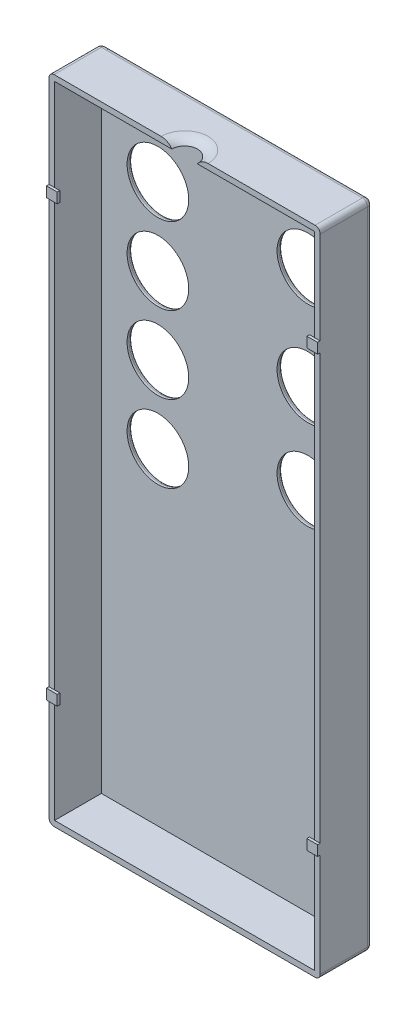
SolidWorks part; units mm, degrees
ref_plane "Plan de face" through (0, 0, 0) normal (0, 0, 1) x (1, 0, 0)
ref_plane "Plan de dessus" through (0, 0, 0) normal (0, 1, 0) x (1, 0, 0)
ref_plane "Plan de droite" through (0, 0, 0) normal (1, 0, 0) x (0, 0, -1)
sketch "Esquisse1" plane through (0, 0, 0) normal (0, 0, 1) x (1, 0, 0)
  line L1 (-28.2911, -78.7359) -> (22.3089, -78.7359)
  line L2 (-28.2911, -78.7359) -> (-28.2911, 45.8641)
  line L3 (-28.2911, 45.8641) -> (22.3089, 45.8641)
  line L4 (22.3089, -78.7359) -> (22.3089, 45.8641)
  dimension "D1" = 50.6
  dimension "D2" = 124.6
extrude "Boss.-Extru.1" add sketch "Esquisse1" along normal blind 9.1
shell "Coque7" thickness 1.1 removed face at (-2.9911, -16.4359, 9.1) outward yes
sketch "Esquisse4" plane through (0, 46.9641, 0) normal (0, 1, 0) x (1, 0, 0)
  line L0 (-29.3911, -9.1) -> (-2.9911, -9.1) construction
  line L1 (23.4089, -9.1) -> (-29.3911, -9.1) construction
  line L2 (-2.9911, -9.1) -> (-2.9911, 1.1) construction
  line L3 (23.4089, 1.1) -> (-29.3911, 1.1) construction
  arc A0 (-5.4911, -9.1) -> (-0.4911, -9.1) centre (-2.9911, -9.1) cw
extrude "Enlèv. mat.-Extru.2" cut sketch "Esquisse4" against normal blind 7 and the other way through all flip side to cut
fillet "Congé1" radius 2.5 1 edges at (-2.9911, 46.9641, 6.6)
sketch "Esquisse6" plane through (0, 0, -1.1) normal (0, 0, -1) x (-1, 0, 0)
  line L0 (-23.4089, 46.9641) -> (29.3911, 46.9641) construction
  line L1 (29.3911, 46.9641) -> (29.3911, -79.8359) construction
  line L2 (-23.4089, -79.8359) -> (-23.4089, 46.9641) construction
  circle A0 centre (17.2911, 14.8641) radius 6
  circle A1 centre (17.2911, 29.8641) radius 6
  circle A2 centre (17.2911, -0.1359) radius 6
  circle A3 centre (17.2911, -15.1359) radius 6
  circle A4 centre (-11.9089, 29.8641) radius 6
  circle A5 centre (-11.9089, 9.8641) radius 6
  circle A6 centre (-11.9089, -7.6359) radius 6
  point P18 (-23.4089, 37.6111)
  point P19 (0, 0)
  dimension "D1" = 17.1
  dimension "D2" = 11.5
  dimension "D3" = 37.1
  dimension "D4" = 54.6
  dimension "D5" = 11.5
  dimension "D6" = 11.5
  dimension "D7" = 62.1
  dimension "D8" = 47.1
  dimension "D9" = 17.1
  dimension "D10" = 32.1
  dimension "D11" = 12.1
  dimension "D12" = 12.1
  dimension "D13" = 12.1
  dimension "D14" = 12.1
extrude "Enlèv. mat.-Extru.12" cut sketch "Esquisse6" against normal blind 7
fillet "Congé2" radius 0.7 7 edges at (5.9089, -7.6359, -1.1) (-23.2911, -15.1359, -1.1) (-23.2911, -0.1359, -1.1) (-23.2911, 14.8641, -1.1) (5.9089, 9.8641, -1.1) (5.9089, 29.8641, -1.1) (-23.2911, 29.8641, -1.1)
fillet "Congé3" radius 1 8 edges at (-2.9911, 46.9641, -1.1) (-29.3911, -79.8359, 4) (-2.9911, -79.8359, -1.1) (23.4089, -79.8359, 4) (23.4089, -16.4359, -1.1) (-29.3911, -16.4359, -1.1) (-29.3911, 46.9641, 4) (23.4089, 46.9641, 4)
sketch "Esquisse8" plane through (0, 0, 9.1) normal (0, 0, 1) x (1, 0, 0)
  line L0 (-28.3911, 45.9641) -> (-28.2911, 25.9641)
  line L1 (-28.2911, 45.8641) -> (-28.2911, -78.7359) construction
  line L2 (-28.2911, 25.9641) -> (22.3089, 25.9641) construction
  line L3 (22.3089, -78.7359) -> (22.3089, 45.8641) construction
  line L4 (-28.2911, 25.9641) -> (-28.3011, 27.9641)
  line L5 (-28.3011, 27.9641) -> (-29.3911, 27.9641)
  line L6 (-29.3911, 45.9641) -> (-29.3911, -78.8359) construction
  line L7 (22.3089, 25.9641) -> (23.4089, 25.9641)
  line L8 (-29.3911, 27.9641) -> (-27.2911, 27.9641)
  line L9 (-29.3911, 27.9641) -> (-29.3911, 25.9641)
  line L10 (-29.3911, 25.9641) -> (-27.2911, 25.9641)
  line L11 (-27.2911, 27.9641) -> (-27.2911, 25.9641)
  line L12 (23.4089, -78.8359) -> (23.4089, 45.9641) construction
  line L13 (23.4089, 25.9641) -> (23.4089, 27.9641)
  line L15 (23.4089, 27.9641) -> (21.3089, 27.9641)
  line L16 (23.4089, 27.9641) -> (23.4089, 25.9641)
  line L17 (23.4089, 25.9641) -> (21.3089, 25.9641)
  line L18 (21.3089, 27.9641) -> (21.3089, 25.9641)
  line M7 (23.4089, -78.8359) -> (23.4089, 45.9641)
  line M12 (22.3089, 45.8641) -> (22.3089, -78.7359)
  dimension "D1" = 20
  dimension "D2" = 2
  dimension "D3" = 2.1
  dimension "D4" = 2
  dimension "D5" = 2.1
extrude "Boss.-Extru.3" add sketch "Esquisse8" along normal blind 0.5 contours L15 L7 M7 M12 | L15 L18 L17 M12 | L9 L10 L11 L8 region at (22.8589, 26.9641, 9.1) region at (21.8089, 26.9641, 9.1)
sketch "Esquisse9" plane through (0, 0, 9.1) normal (0, 0, 1) x (1, 0, 0)
  line L0 (-28.2911, -78.7359) -> (-28.2911, -58.7359) construction
  line L1 (-28.2911, 25.9641) -> (-28.2911, -78.7359) construction
  line L2 (-28.2911, -58.7359) -> (22.3089, -58.7359) construction
  line L3 (22.3089, -78.7359) -> (22.3089, 25.9641) construction
  line L4 (22.3089, -58.7359) -> (23.4089, -58.7359) construction
  line L5 (23.4089, -78.8359) -> (23.4089, 25.9641) construction
  line L6 (23.4089, -58.7359) -> (23.4089, -56.7359) construction
  line L7 (-28.2911, -58.7359) -> (-29.3911, -58.7359) construction
  line L8 (-29.3911, 25.9641) -> (-29.3911, -78.8359) construction
  line L9 (-29.3911, -58.7359) -> (-29.3911, -56.7359) construction
  line L11 (23.4089, -58.7359) -> (21.3089, -58.7359)
  line L12 (23.4089, -58.7359) -> (23.4089, -56.7359)
  line L13 (23.4089, -56.7359) -> (21.3089, -56.7359)
  line L14 (21.3089, -58.7359) -> (21.3089, -56.7359)
  line L15 (-29.3911, -58.7359) -> (-27.2911, -58.7359)
  line L16 (-29.3911, -58.7359) -> (-29.3911, -56.7359)
  line L17 (-29.3911, -56.7359) -> (-27.2911, -56.7359)
  line L18 (-27.2911, -58.7359) -> (-27.2911, -56.7359)
  dimension "D1" = 20
  dimension "D2" = 2
  dimension "D3" = 2
  dimension "D4" = 2.1
  dimension "D5" = 2
  dimension "D6" = 2.1
extrude "Boss.-Extru.4" add sketch "Esquisse9" along normal blind 0.5
